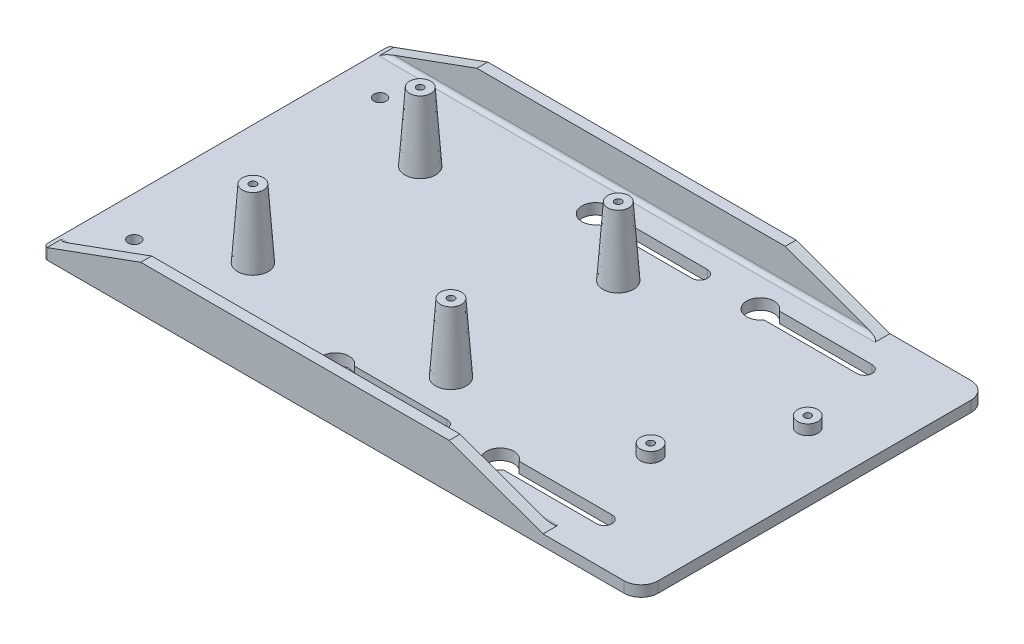
SolidWorks part; units mm, degrees
ref_plane "Front Plane" through (0, 0, 0) normal (0, 0, 1) x (1, 0, 0)
ref_plane "Top Plane" through (0, 0, 0) normal (0, 1, 0) x (1, 0, 0)
ref_plane "Right Plane" through (0, 0, 0) normal (1, 0, 0) x (0, 0, -1)
sketch "Sketch1" plane through (0, 0, 0) normal (0, 1, 0) x (1, 0, 0)
  line L0 (0, 0) -> (175, 0) construction
  line L1 (0, 50.8) -> (175, 50.8)
  line L2 (0, 50.8) -> (0, -50.8)
  line L3 (0, -50.8) -> (175, -50.8)
  line L4 (175, 50.8) -> (175, -50.8)
  line L5 (0, 50.8) -> (175, -50.8) construction
  line L6 (0, -50.8) -> (175, 50.8) construction
  point P0 (11.3289, 32.4526)
  point P5 (0, 0)
  dimension "D1" = 101.6
  dimension "D2" = 175
extrude "plate" add sketch "Sketch1" along normal blind 3.175
sketch "Sketch14" plane through (0, 0, 0) normal (0, -1, 0) x (1, 0, 0)
  text T0 "BOTTOM" font "Century Gothic" height 3.5
extrude "bottom label" cut sketch "Sketch14" against normal blind 0.6
hole_wizard "mount slots" positions "Sketch8" profile "Sketch9" size "M4" standard "ISO" slot yes end condition through all
sketch "Sketch8" plane through (0, 3.175, 0) normal (0, 1, 0) x (1, 0, 0)
  line L0 (88, 38.1) -> (136.26, 38.1) construction
  line L2 (0, 0) -> (175, 0) construction
  line L3 (175, -50.8) -> (175, 50.8) construction
  line L4 (0, 50.8) -> (0, -50.8) construction
  line L5 (88, -38.1) -> (136.26, -38.1) construction
  line L6 (70.5, 38.1) -> (105.5, 38.1) construction
  point P1 (88, 38.1)
  point P2 (136.26, 38.1)
  point P23 (136.26, -38.1)
  point P24 (88, -38.1)
  dimension "D1" = 48.26
  dimension "D2" = 38.1
  dimension "D3" = 88
  dimension "D4" = 35
sketch "Sketch9" plane through (88, 3.175, -38.1) normal (1, 0, 0) x (0, 0, 1)
  line L0 (0, 0) -> (0, 3.175)
  line L1 (0, 3.175) -> (2.25, 3.175)
  line L2 (2.25, 3.175) -> (2.25, 0)
  line L5 (2.25, 0) -> (0, 0)
  line L11 (0, -6.35) -> (0, 107.95) construction
  dimension "Thru Hole Dia." = 4.5
  dimension "Thru Hole Depth" = 3.175
sketch "Sketch12" plane through (0, 3.175, 0) normal (0, 1, 0) x (1, 0, 0)
  line L0 (-12.7462, 0) -> (12.7462, 0) construction
  circle A0 centre (121.01, 38.1) radius 4
  circle A1 centre (72.75, 38.1) radius 4
  circle A5 centre (72.75, -38.1) radius 4
  circle A6 centre (121.01, -38.1) radius 4
  arc A7 (72.75, 40.35) -> (72.75, 35.85) centre (72.75, 38.1) ccw construction
  arc A8 (121.01, 40.35) -> (121.01, 35.85) centre (121.01, 38.1) ccw construction
  dimension "D1" = 8
  dimension "D2" = 8
extrude "slot_clearance" cut sketch "Sketch12" against normal through all
hole_wizard "bracket  holes" positions "Sketch10" profile "Sketch11" hole size "M3" standard "ISO" end condition through all
sketch "Sketch10" plane through (0, 3.175, 0) normal (0, 1, 0) x (1, 0, 0)
  line L0 (0, 0) -> (175, 0) construction
  line L1 (0, 50.8) -> (0, -50.8) construction
  line L2 (175, -50.8) -> (175, 50.8) construction
  point P0 (11.75, 36)
  point P14 (11.75, -36)
  dimension "D1" = 11.75
  dimension "D2" = 36
sketch "Sketch11" plane through (11.75, 3.175, -36) normal (1, 0, 0) x (0, 0, 1)
  line L0 (0, 0) -> (0, 3.175)
  line L1 (0, 3.175) -> (1.8, 3.175)
  line L2 (1.8, 3.175) -> (1.8, 0)
  line L5 (1.8, 0) -> (0, 0)
  line L11 (0, -6.35) -> (0, 107.95) construction
  dimension "Thru Hole Dia." = 3.6
  dimension "Thru Hole Depth" = 3.175
sketch "Sketch13" plane through (0, 0, -50.8) normal (0, 0, -1) x (-1, 0, 0)
  line L0 (-146.26, 3.175) -> (-118.7852, 13.175)
  line L1 (-175, 3.175) -> (0, 3.175) construction
  line L2 (-118.7852, 13.175) -> (-28.4748, 13.175)
  line L3 (-28.4748, 13.175) -> (-1, 3.175)
  line L4 (-1, 3.175) -> (-146.26, 3.175)
  line L6 (0, 3.175) -> (0, 0) construction
  point P10 (0, 1.5875)
  dimension "D1" = 20
  dimension "D2" = 10
  dimension "D3" = 20
  dimension "D4" = 1
  dimension "D5" = 10
extrude "plate stiffener" add sketch "Sketch13" against normal blind 3.175
mirror "stiffener mirror" about plane through (0, 0, 0) normal (0, 0, 1) of "plate stiffener"
sketch "Sketch15" plane through (0, 3.175, 0) normal (0, 1, 0) x (1, 0, 0)
  line L1 (0, 0) -> (102.1318, 0) construction
  line L2 (64, 24.5) -> (64, 0) construction
  line L3 (35, 24.5) -> (93, 24.5) construction
  line L4 (-12.7462, 0) -> (12.7462, 0) construction
  circle A1 centre (93, 24.5) radius 4.5
  circle A2 centre (35, 24.5) radius 4.5
  circle A3 centre (35, -24.5) radius 4.5
  circle A4 centre (93, -24.5) radius 4.5
  point P7 (0, 0)
  point P9 (0, 0)
  point P17 (0, 0)
  point P18 (0, 0)
  dimension "D1" = 9
  dimension "D4" = 58
  dimension "D2" = 35
  dimension "D3" = 24.5
extrude "pi standoffs" add sketch "Sketch15" along normal blind 20 draft 4
hole_wizard "pi hole M2.5 tapped" positions "Sketch18" profile "Sketch19" hole size "M2.5" standard "ISO" end condition through all
sketch "Sketch18" plane through (0, 23.175, 0) normal (0, 1, 0) x (1, 0, 0)
  circle A0 centre (93, -24.5) radius 3.1015 construction
  circle A1 centre (35, -24.5) radius 3.1015 construction
  circle A2 centre (35, 24.5) radius 3.1015 construction
  circle A3 centre (93, 24.5) radius 3.1015 construction
  point P0 (35, -24.5)
  point P2 (35, 24.5)
  point P4 (93, 24.5)
  point P6 (93, -24.5)
  point P7 (0, 0)
  point P10 (0, 0)
  point P11 (0, 0)
  point P14 (0, 0)
  point P17 (0, 0)
sketch "Sketch19" plane through (35, 23.175, 24.5) normal (1, 0, 0) x (0, 0, 1)
  line L0 (0, 0) -> (0, 23.175)
  line L1 (0, 23.175) -> (1.025, 23.175)
  line L2 (1.025, 23.175) -> (1.025, 0)
  line L5 (1.025, 0) -> (0, 0)
  line L11 (0, -6.35) -> (0, 107.95) construction
  dimension "Thru Hole Dia." = 2.05
  dimension "Thru Hole Depth" = 23.175
sketch "Sketch20" plane through (0, 3.175, 0) normal (0, 1, 0) x (1, 0, 0)
  line L0 (0, 0) -> (175, 0) construction
  line L1 (142, -15) -> (158, -15) construction
  line L2 (142, -15) -> (142, 15) construction
  line L3 (142, 15) -> (158, 15) construction
  line L4 (158, -15) -> (158, 15) construction
  line L5 (0, 50.8) -> (0, -50.8) construction
  line L7 (175, -50.8) -> (175, 50.8) construction
  circle A0 centre (158, 15) radius 3
  circle A1 centre (142, -15) radius 3
  point P0 (158, 15)
  point P1 (142, -15)
  point P8 (142, 0)
  point P9 (158, 0)
  point P14 (0, 0)
  dimension "D4" = 6
  dimension "D5" = 6
  dimension "D1" = 16
  dimension "D2" = 30
  dimension "D3" = 142
extrude "reg standoffs" add sketch "Sketch20" along normal blind 3
hole_wizard "reg hole M2.5 tapped" positions "Sketch21" profile "Sketch22" hole size "M2.5" standard "ISO" end condition through all
sketch "Sketch21" plane through (0, 6.175, 0) normal (0, 1, 0) x (1, 0, 0)
  circle A0 centre (158, 15) radius 3 construction
  circle A1 centre (142, -15) radius 3 construction
  point P0 (142, -15)
  point P2 (158, 15)
  point P5 (0, 0)
  point P8 (0, 0)
sketch "Sketch22" plane through (142, 6.175, 15) normal (1, 0, 0) x (0, 0, 1)
  line L0 (0, 0) -> (0, 6.175)
  line L1 (0, 6.175) -> (1.025, 6.175)
  line L2 (1.025, 6.175) -> (1.025, 0)
  line L5 (1.025, 0) -> (0, 0)
  line L11 (0, -6.35) -> (0, 107.95) construction
  dimension "Thru Hole Dia." = 2.05
  dimension "Thru Hole Depth" = 6.175
fillet "Fillet 1.2mm" radius 1.2 4 edges at (73.63, 3.175, 47.625) (73.63, 3.175, -47.625) (0, 1.5875, -50.8) (0, 1.5875, 50.8)
fillet "Fillet2" radius 5 2 edges at (175, 1.5875, 50.8) (175, 1.5875, -50.8)
